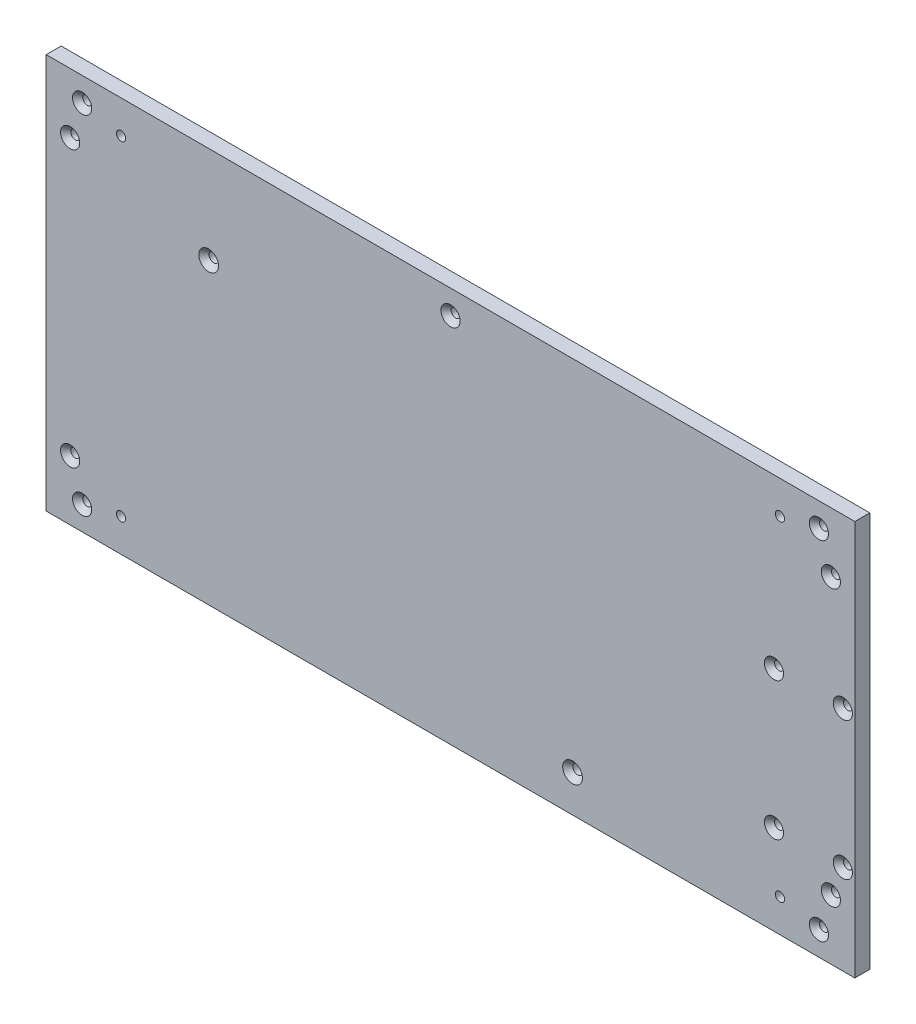
SolidWorks part; units mm, degrees
ref_plane "Front Plane" through (0, 0, 0) normal (0, 0, 1) x (1, 0, 0)
ref_plane "Top Plane" through (0, 0, 0) normal (0, 1, 0) x (1, 0, 0)
ref_plane "Right Plane" through (0, 0, 0) normal (1, 0, 0) x (0, 0, -1)
sketch "Sketch1" plane through (0, 0, 0) normal (0, 0, 1) x (1, 0, 0)
  line L1 (135, -66) -> (-135, -66)
  line L2 (135, -66) -> (135, 66)
  line L3 (135, 66) -> (-135, 66)
  line L4 (-135, -66) -> (-135, 66)
  line L5 (135, -66) -> (-135, 66) construction
  line L6 (135, 66) -> (-135, -66) construction
  point P0 (0, 0)
  dimension "D1" = 270
  dimension "D2" = 132
extrude "Base" add sketch "Sketch1" along normal mid plane 5 contours L4 L1 L2 L3 region at (0, 0, 0)
sketch "Sketch2" plane through (0, 0, 2.5) normal (0, 0, 1) x (1, 0, 0)
  line L0 (135, 66) -> (-135, 66) construction
  line L1 (135, -66) -> (135, 66) construction
  line L2 (-135, -66) -> (-135, 66) construction
  line L3 (135, -66) -> (-135, -66) construction
  circle A0 centre (-127, -46) radius 1.5
  circle A1 centre (-123, -58) radius 1.5
  circle A2 centre (-127, 46) radius 1.5
  circle A3 centre (-123, 58) radius 1.5
  circle A5 centre (0, 58) radius 1.5
  circle A6 centre (123, -58) radius 1.5
  circle A7 centre (127, -46) radius 1.5
  circle A8 centre (127, 46) radius 1.5
  circle A9 centre (123, 58) radius 1.5
  dimension "D5" = 8
  dimension "D10" = 3
  dimension "D2" = 8
  dimension "D3" = 12
  dimension "D4" = 12
  dimension "D6" = 20
  dimension "D7" = 20
  dimension "D8" = 8
  dimension "D9" = 8
extrude "FastenersHoles" cut sketch "Sketch2" against normal through all
sketch "Sketch3" plane through (0, 0, -2.5) normal (0, 0, -1) x (-1, 0, 0)
  line L3 (80.75, -53.65) -> (-40.75, -53.65) construction
  line L4 (80.75, -53.65) -> (80.75, 33.65) construction
  line L5 (80.75, 33.65) -> (-40.75, 33.65) construction
  line L6 (-40.75, -53.65) -> (-40.75, 33.65) construction
  line L7 (80.75, -53.65) -> (-40.75, 33.65) construction
  line L8 (80.75, 33.65) -> (-40.75, -53.65) construction
  circle A0 centre (-40.75, -53.65) radius 1.6
  circle A1 centre (80.75, 33.65) radius 1.6
  point P0 (16.4091, -11.4342)
  point P2 (20, -10)
  point P3 (77.6346, 33.1029)
  point P4 (-77.6346, -33.7243)
  dimension "D3" = 3.2
  dimension "D1" = 121.5
  dimension "D2" = 87.3
  dimension "D4" = 10
  dimension "D5" = 20
extrude "PSUMount" cut sketch "Sketch3" against normal through all
sketch "Sketch4" plane through (0, 0, 2.5) normal (0, 0, 1) x (1, 0, 0)
  line L1 (131, 10) -> (108, 10) construction
  line L2 (131, 10) -> (131, -36) construction
  line L3 (131, -36) -> (108, -36) construction
  line L4 (108, 10) -> (108, -36) construction
  line L5 (131, 10) -> (108, -36) construction
  line L6 (131, -36) -> (108, 10) construction
  line L7 (135, -66) -> (135, 66) construction
  circle A0 centre (108, 10) radius 1.5
  circle A1 centre (131, 10) radius 1.5
  circle A2 centre (108, -36) radius 1.5
  circle A3 centre (131, -36) radius 1.5
  point P0 (119.5, -13)
  point P16 (135, 0)
  dimension "D5" = 3
  dimension "D1" = 46
  dimension "D2" = 23
  dimension "D3" = 4
  dimension "D4" = 13
extrude "InterfaceHoles" cut sketch "Sketch4" against normal through all
chamfer "ChamferAll" distance 1.7 angle 45 15 edges at (39.15, -53.65, 2.5) (-121.5, -58, 2.5) (-125.5, -46, 2.5) (-121.5, 58, 2.5) (-125.5, 46, 2.5) (-82.35, 33.65, 2.5) (1.5, 58, 2.5) (124.5, 58, 2.5) (128.5, 46, 2.5) (128.5, -46, 2.5) (124.5, -58, 2.5) (132.5, 10, 2.5) (132.5, -36, 2.5) (109.5, -36, 2.5) (109.5, 10, 2.5)
sketch "Sketch5" plane through (0, 0, 2.5) normal (0, 0, 1) x (1, 0, 0)
  line L1 (110, -55) -> (-110, -55) construction
  line L2 (110, -55) -> (110, 55) construction
  line L3 (110, 55) -> (-110, 55) construction
  line L4 (-110, -55) -> (-110, 55) construction
  line L5 (110, -55) -> (-110, 55) construction
  line L6 (110, 55) -> (-110, -55) construction
  circle A0 centre (-110, -55) radius 1.55
  circle A1 centre (-110, 55) radius 1.55
  circle A2 centre (110, 55) radius 1.55
  circle A3 centre (110, -55) radius 1.55
  point P8 (0, 0)
  dimension "D1" = 3.1
  dimension "D2" = 110
  dimension "D3" = 220
extrude "Cut-Extrude2" cut sketch "Sketch5" against normal through all
